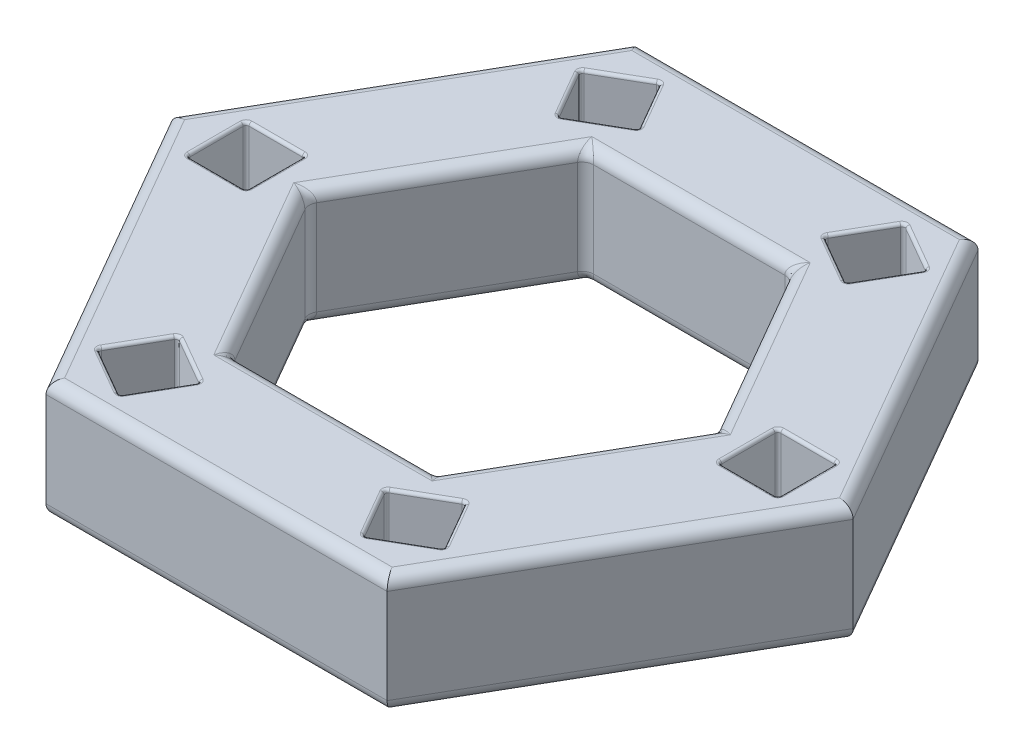
SolidWorks part; units mm, degrees
ref_plane "Front" through (0, 0, 0) normal (0, 0, 1) x (1, 0, 0)
ref_plane "Top" through (0, 0, 0) normal (0, 1, 0) x (1, 0, 0)
ref_plane "Right" through (0, 0, 0) normal (1, 0, 0) x (0, 0, -1)
ref_plane "Plane1" through (0, -10, 0) normal (0, -1, 0) x (1, 0, 0)
sketch "Sketch1" plane through (0, -10, 0) normal (0, -1, 0) x (1, 0, 0)
  line L0 (14.4338, -25) -> (28.8675, 0)
  line L1 (28.8675, 0) -> (14.4338, 25)
  line L2 (14.4338, 25) -> (-14.4338, 25)
  line L3 (-14.4338, 25) -> (-28.8675, 0)
  line L4 (-28.8675, 0) -> (-14.4338, -25)
  line L5 (-14.4338, -25) -> (14.4338, -25)
  line L6 (-8.6603, -15) -> (8.6603, -15)
  line L7 (8.6603, -15) -> (17.3205, 0)
  line L8 (17.3205, 0) -> (8.6603, 15)
  line L9 (8.6603, 15) -> (-8.6603, 15)
  line L10 (-8.6603, 15) -> (-17.3205, 0)
  line L11 (-17.3205, 0) -> (-8.6603, -15)
  circle A0 centre (0, 0) radius 25 construction
  dimension "D1" = 50
  dimension "D2" = 10
extrude "Boss-Extrude1" add sketch "Sketch1" against normal blind 10
fillet "Fillet1" radius 1 24 edges at (0, -10, -15) (12.9904, -10, -7.5) (12.9904, -10, 7.5) (0, -10, 15) (-12.9904, -10, 7.5) (-12.9904, -10, -7.5) (-21.6506, -10, -12.5) (-21.6506, -10, 12.5) (0, -10, 25) (21.6506, -10, 12.5) (21.6506, -10, -12.5) (0, -10, -25) (0, 0, 15) (12.9904, 0, 7.5) (12.9904, 0, -7.5) (0, 0, -15) (-12.9904, 0, -7.5) (-12.9904, 0, 7.5) (21.6506, 0, -12.5) (21.6506, 0, 12.5) (0, 0, 25) (-21.6506, 0, 12.5) (-21.6506, 0, -12.5) (0, 0, -25)
fillet "Fillet2" radius 1 18 edges at (-8.8294, -0.2929, 15.2929) (-8.8294, -9.7071, 15.2929) (8.8294, -0.2929, 15.2929) (8.8294, -9.7071, 15.2929) (17.6587, -0.2929, 0) (17.6587, -9.7071, 0) (8.8294, -0.2929, -15.2929) (8.8294, -9.7071, -15.2929) (-8.8294, -0.2929, -15.2929) (-8.8294, -9.7071, -15.2929) (-17.6587, -0.2929, 0) (-17.6587, -9.7071, 0) (-8.6603, -5, 15) (8.6603, -5, 15) (17.3205, -5, 0) (8.6603, -5, -15) (-8.6603, -5, -15) (-17.3205, -5, 0)
sketch "Sketch2" plane through (0, 0, 0) normal (0, 1, 0) x (-1, 0, 0)
  line L0 (-20, 2.5) -> (-25, 2.5)
  line L1 (-25, 2.5) -> (-25, -2.5)
  line L2 (-25, -2.5) -> (-20, -2.5)
  line L3 (-20, -2.5) -> (-20, 2.5)
  line L4 (-20, -2.5) -> (-25, 2.5) construction
  line L5 (-25, -2.5) -> (-20, 2.5) construction
  point P8 (-22.5, 0)
  dimension "D1" = 5
  dimension "D2" = 22.5
extrude "Cut-Extrude1" cut sketch "Sketch2" against normal through all
fillet "Fillet3" radius 0.25 12 edges at (25, 0, 0) (22.5, 0, -2.5) (22.5, 0, 2.5) (20, 0, 0) (25, -10, 0) (22.5, -10, -2.5) (22.5, -10, 2.5) (20, -10, 0) (20, -5, 2.5) (20, -5, -2.5) (25, -5, -2.5) (25, -5, 2.5) tangent propagation no
ref_axis "Axis2" through (0, 50, 0) along (0, -1, 0)
pattern_circular "CirPattern1" count 6 over 360 about axis through (0, 50, 0) along (0, -1, 0) of "Cut-Extrude1", "Fillet3"
